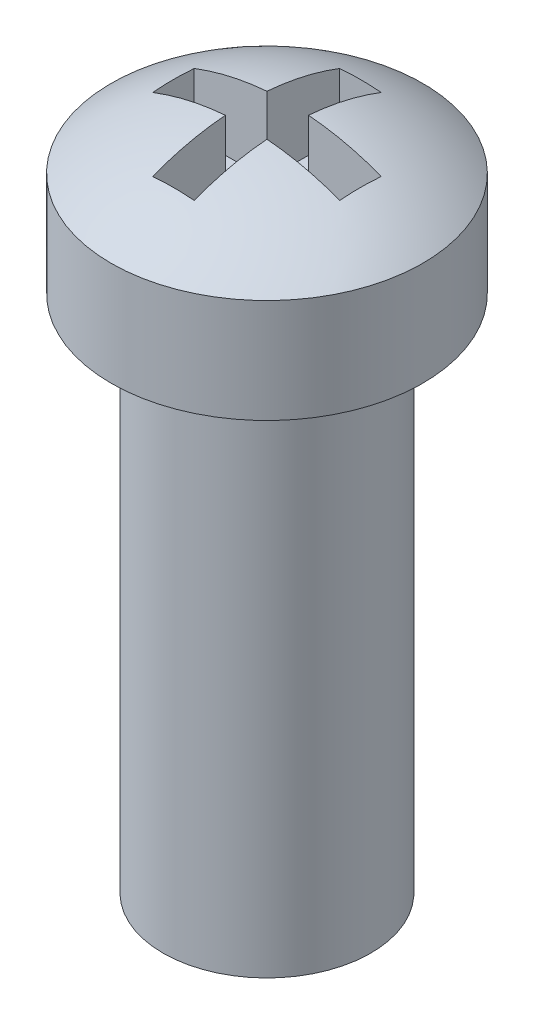
SolidWorks part; units mm, degrees
material "1023 Carbon Steel Sheet (SS)"
ref_plane "Front Plane" through (0, 0, 0) normal (0, 0, 1) x (1, 0, 0)
ref_plane "Top Plane" through (0, 0, 0) normal (0, 1, 0) x (1, 0, 0)
ref_plane "Right Plane" through (0, 0, 0) normal (1, 0, 0) x (0, 0, -1)
ref_plane "Top Plane1" through (0, 6.5, 0) normal (0, 1, 0) x (1, 0, 0)
sketch "Sketch1" plane through (0, 0, 0) normal (0, 1, 0) x (1, 0, 0)
  circle A0 centre (0, 0) radius 1
  dimension "D1" = 2
extrude "Boss-Extrude1" add sketch "Sketch1" along normal blind 5
sketch "Sketch2" plane through (0, 5, 0) normal (0, 1, 0) x (1, 0, 0)
  circle A0 centre (0, 0) radius 1.5
  dimension "D1" = 3
extrude "Boss-Extrude2" add sketch "Sketch2" along normal blind 1
dome "Dome1" faces to dome 1 distance 0.5 reverse direction no elliptical dome no face at (0, 6, 1.5) parameters "D1"=0.5
sketch "Sketch3" plane through (0, 6.5, 0) normal (0, 1, 0) x (1, 0, 0)
  line L0 (-1.5, 0) -> (1.5, 0) construction
  line L1 (0, 1.5) -> (0, -1.5) construction
  line L2 (-0.9, 0.2) -> (0.9, -0.2) construction
  line L3 (-0.9, 0.2) -> (0.9, 0.2)
  line L4 (-0.9, 0.2) -> (-0.9, -0.2)
  line L5 (-0.9, -0.2) -> (0.9, -0.2)
  line L6 (0.9, 0.2) -> (0.9, -0.2)
  line L7 (0.2, 0.9) -> (-0.2, -0.9) construction
  line L8 (-0.2, 0.9) -> (0.2, 0.9)
  line L9 (-0.2, 0.9) -> (-0.2, -0.9)
  line L10 (-0.2, -0.9) -> (0.2, -0.9)
  line L11 (0.2, 0.9) -> (0.2, -0.9)
  circle A0 centre (0, 0) radius 1.5 construction
  dimension "D1" = 0.9
  dimension "D2" = 0.9
  dimension "D3" = 0.4
  dimension "D4" = 0.4
extrude "Cut-Extrude1" cut sketch "Sketch3" against normal blind 0.75 contours L9 L3 L4 L5 | L11 L3 L9 L5 | L11 L8 L9 L3 | L3 L11 L5 L6 | L11 L5 L9 L10 region at (-0.55, 6.5, 0) region at (0, 6.5, -0.55) region at (0, 6.5, 0) region at (0.55, 6.5, 0) region at (0, 6.5, 0.55)
